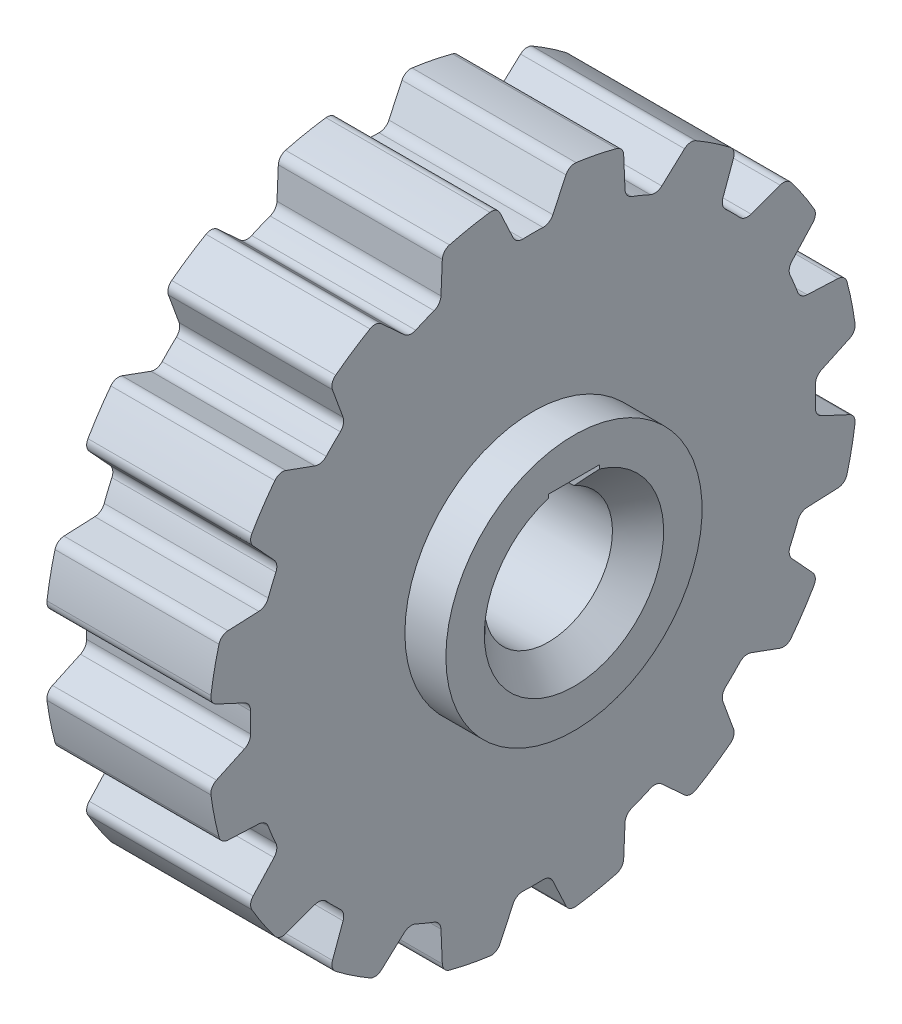
SolidWorks part; units mm, degrees
ref_plane "前视基准面" through (0, 0, 0) normal (0, 0, 1) x (1, 0, 0)
ref_plane "上视基准面" through (0, 0, 0) normal (0, 1, 0) x (1, 0, 0)
ref_plane "右视基准面" through (0, 0, 0) normal (1, 0, 0) x (0, 0, -1)
sketch "草图1" plane through (0, 0, 0) normal (0, 0, 1) x (1, 0, 0)
  line L0 (0, 0) -> (64.8368, 0) construction
  line L1 (0, 2.5) -> (0, 12.681)
  line L2 (0, 12.681) -> (6.4, 12.681)
  line L3 (6.4, 12.681) -> (6.4, 5)
  line L4 (6.4, 5) -> (8, 5)
  line L5 (8, 5) -> (8, 2.5)
  line L6 (8, 2.5) -> (0, 2.5)
  dimension "L" = 8
  dimension "B" = 6.4
  dimension "d" = 5
  dimension "d1" = 10
  dimension "da" = 25.362
revolve "旋转1" add sketch "草图1" angle 360 about L0
chamfer "倒角1" distance 1 angle 45 2 edges at (8, 0, 2.5) (0, 0, 2.5)
sketch "草图4" plane through (0, 0, 0) normal (-1, 0, 0) x (0, 0, 1)
  line L1 (-1, 2.2913) -> (1, 2.2913)
  line L2 (-1, 2.2913) -> (-1, 3.5)
  line L3 (-1, 3.5) -> (1, 3.5)
  line L4 (1, 2.2913) -> (1, 3.5)
  circle A0 centre (0, 0) radius 2.5 construction
  point P6 (0, 3.5)
  dimension "键槽高度" = 3.5
  dimension "键槽宽度" = 2
  dimension "t1" = 1
extrude "切除-拉伸1" cut sketch "草图4" against normal through all
ref_axis "基准轴1" through (-1.4, 0, 0) along (1, 0, 0)
sketch "草图6" plane through (0, 0, 0) normal (1, 0, 0) x (0, 0, -1)
  line L0 (0, 0) -> (0, 16.0158) construction
  line L1 (1.2857, 12.3531) -> (0.7763, 11.2606)
  line L2 (2.0563, 12.5132) -> (2.6718, 13.8331)
  line L3 (-2.0563, 12.5132) -> (-2.6718, 13.8331)
  line L4 (-1.2857, 12.3531) -> (-0.7763, 11.2606)
  circle A0 centre (0, 0) radius 12.681 construction
  arc A1 (0.3902, 11.0241) -> (-0.3902, 11.0241) centre (0, 0) ccw
  arc A2 (1.6805, 12.5692) -> (2.0563, 12.5132) centre (0, 0) cw
  arc A3 (0.7763, 11.2606) -> (0.3902, 11.0241) centre (0.4047, 11.4338) cw
  arc A4 (1.2857, 12.3531) -> (1.6805, 12.5692) centre (1.6301, 12.1925) cw
  arc A5 (2.6718, 13.8331) -> (-2.6718, 13.8331) centre (0, 0) ccw
  arc A6 (-1.6805, 12.5692) -> (-2.0563, 12.5132) centre (0, 0) ccw
  arc A7 (-1.2857, 12.3531) -> (-1.6805, 12.5692) centre (-1.6301, 12.1925) ccw
  arc A8 (-0.7763, 11.2606) -> (-0.3902, 11.0241) centre (-0.4047, 11.4338) ccw
  point P8 (0, 14.3658)
  point P14 (1.4024, 12.6032)
  point P16 (0.66, 11.0112)
  dimension "D1" = 11.031
  dimension "ra" = 0.38
  dimension "rf" = 0.41
  dimension "D3" = 1.4563
  dimension "D4" = 0.38
  dimension "bw" = 1.32
  dimension "angle" = 50
  dimension "hg" = 1.65
extrude "切除-拉伸2" cut sketch "草图6" along normal up to next
pattern_circular "阵列(圆周)3" count 16 over 360 about axis through (-1.4, 0, 0) along (1, 0, 0) of "切除-拉伸2"
equation "\"键槽高度@草图4\" = \"d@草图1\" / 2  + \"t1@草图4\""
equation "\"D4@草图6\" = \"ra@草图6\""
equation "\"D1@草图6\" = \"da@草图1\" / 2 - \"hg@草图6\" "
